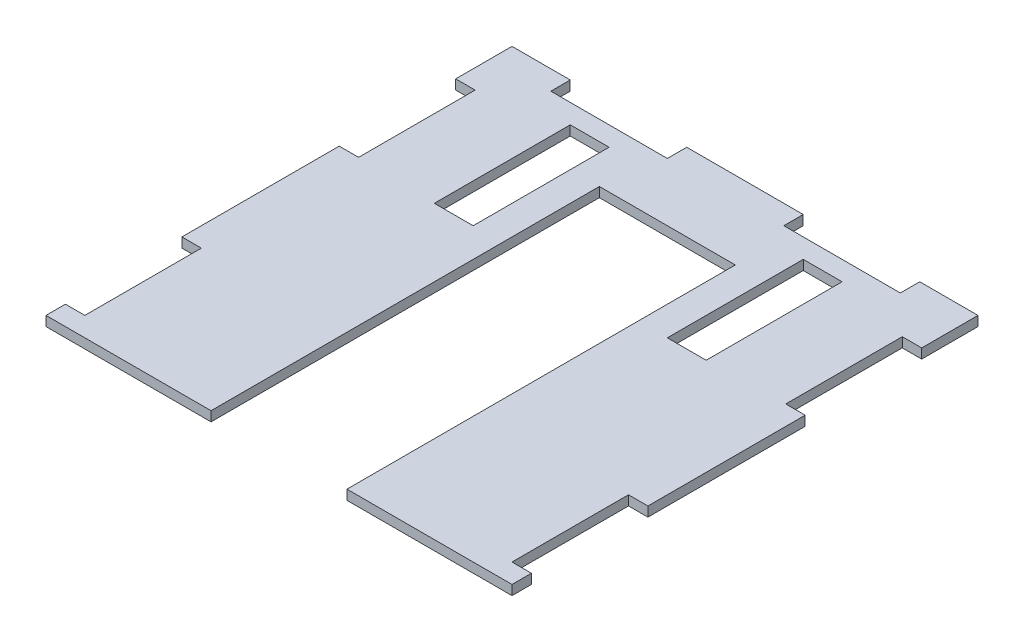
SolidWorks part; units mm, degrees
ref_plane "Front Plane" through (0, 0, 0) normal (0, 0, 1) x (1, 0, 0)
ref_plane "Top Plane" through (0, 0, 0) normal (0, 1, 0) x (1, 0, 0)
ref_plane "Right Plane" through (0, 0, 0) normal (1, 0, 0) x (0, 0, -1)
sketch "Sketch1" plane through (0, 0, 0) normal (0, 1, 0) x (1, 0, 0)
  line L0 (0, -55) -> (0, 55) construction
  line L1 (-152.4, -25.4) -> (152.4, -25.4)
  line L2 (-152.4, -25.4) -> (-152.4, 25.4)
  line L3 (-152.4, 25.4) -> (152.4, 25.4)
  line L4 (152.4, -25.4) -> (152.4, 25.4)
  line L5 (-152.4, -25.4) -> (152.4, 25.4) construction
  line L6 (-152.4, 25.4) -> (152.4, -25.4) construction
  line L7 (-152.4, -25.4) -> (-31.75, -25.4)
  line L8 (-152.4, -25.4) -> (-152.4, -279.4)
  line L9 (-152.4, -279.4) -> (-31.75, -279.4)
  line L10 (-31.75, -25.4) -> (-31.75, -279.4)
  line L11 (31.75, -25.4) -> (31.75, -279.4)
  line L12 (152.4, -279.4) -> (31.75, -279.4)
  line L13 (152.4, -25.4) -> (152.4, -279.4)
  line L14 (152.4, -25.4) -> (31.75, -25.4)
  line L15 (-44.45, -25.4) -> (-44.45, -279.4)
  line L16 (44.45, -25.4) -> (44.45, -279.4)
  point P0 (0, 0)
  dimension "D1" = 304.8
  dimension "D2" = 50.8
  dimension "D3" = 304.8
  dimension "D4" = 120.65
  dimension "D5" = 12.7
extrude "Boss-Extrude1" add sketch "Sketch1" along normal blind 6.35 contours L15 L1 L8 L9 | L14 L16 L12 L13 | L1 L7 L14 L4 L3 L2 region at (0, 0, 0) region at (-98.425, 0, 152.4) region at (98.425, 0, 152.4)
sketch "Sketch2" plane through (0, 6.35, 0) normal (0, 1, 0) x (1, 0, 0)
  line L0 (152.4, -279.4) -> (152.4, 25.4) construction
  line L1 (152.4, -11.43) -> (139.7, -11.43)
  line L2 (152.4, -11.43) -> (152.4, -87.63)
  line L3 (152.4, -87.63) -> (139.7, -87.63)
  line L4 (139.7, -11.43) -> (139.7, -87.63)
  line L5 (-152.4, 25.4) -> (152.4, 25.4) construction
  line L6 (152.4, -190.5) -> (139.7, -190.5)
  line L7 (152.4, -190.5) -> (152.4, -266.7)
  line L8 (152.4, -266.7) -> (139.7, -266.7)
  line L9 (139.7, -190.5) -> (139.7, -266.7)
  line L10 (0, -3.4925) -> (0, 3.4925) construction
  line L11 (-152.4, -266.7) -> (-139.7, -266.7)
  line L12 (-139.7, -190.5) -> (-139.7, -266.7)
  line L13 (-152.4, -190.5) -> (-139.7, -190.5)
  line L14 (-152.4, -190.5) -> (-152.4, -266.7)
  line L15 (-152.4, -87.63) -> (-139.7, -87.63)
  line L16 (-139.7, -11.43) -> (-139.7, -87.63)
  line L17 (-152.4, -11.43) -> (-139.7, -11.43)
  line L18 (-152.4, -11.43) -> (-152.4, -87.63)
  line L19 (-114.3, 12.7) -> (-38.1, 12.7)
  line L20 (114.3, 25.4) -> (38.1, 25.4)
  line L21 (114.3, 25.4) -> (114.3, 12.7)
  line L22 (114.3, 12.7) -> (38.1, 12.7)
  line L23 (38.1, 25.4) -> (38.1, 12.7)
  line L24 (-38.1, 25.4) -> (-38.1, 12.7)
  line L25 (-114.3, 25.4) -> (-38.1, 25.4)
  line L26 (-114.3, 25.4) -> (-114.3, 12.7)
  line L27 (-88.9, -88.9) -> (-63.5, -88.9)
  line L28 (88.9, 0) -> (63.5, 0)
  line L29 (88.9, 0) -> (88.9, -88.9)
  line L30 (88.9, -88.9) -> (63.5, -88.9)
  line L31 (63.5, 0) -> (63.5, -88.9)
  line L32 (-63.5, 0) -> (-63.5, -88.9)
  line L33 (-88.9, 0) -> (-63.5, 0)
  line L34 (-88.9, 0) -> (-88.9, -88.9)
  dimension "D1" = 12.7
  dimension "D2" = 12.7
  dimension "D3" = 76.2
  dimension "D4" = 76.2
  dimension "D5" = 36.83
  dimension "D6" = 215.9
  dimension "D7" = 76.2
  dimension "D8" = 12.7
  dimension "D9" = 76.2
  dimension "D10" = 25.4
  dimension "D11" = 114.3
  dimension "D12" = 63.5
  dimension "D13" = 88.9
extrude "Cut-Extrude1" cut sketch "Sketch2" against normal through all
